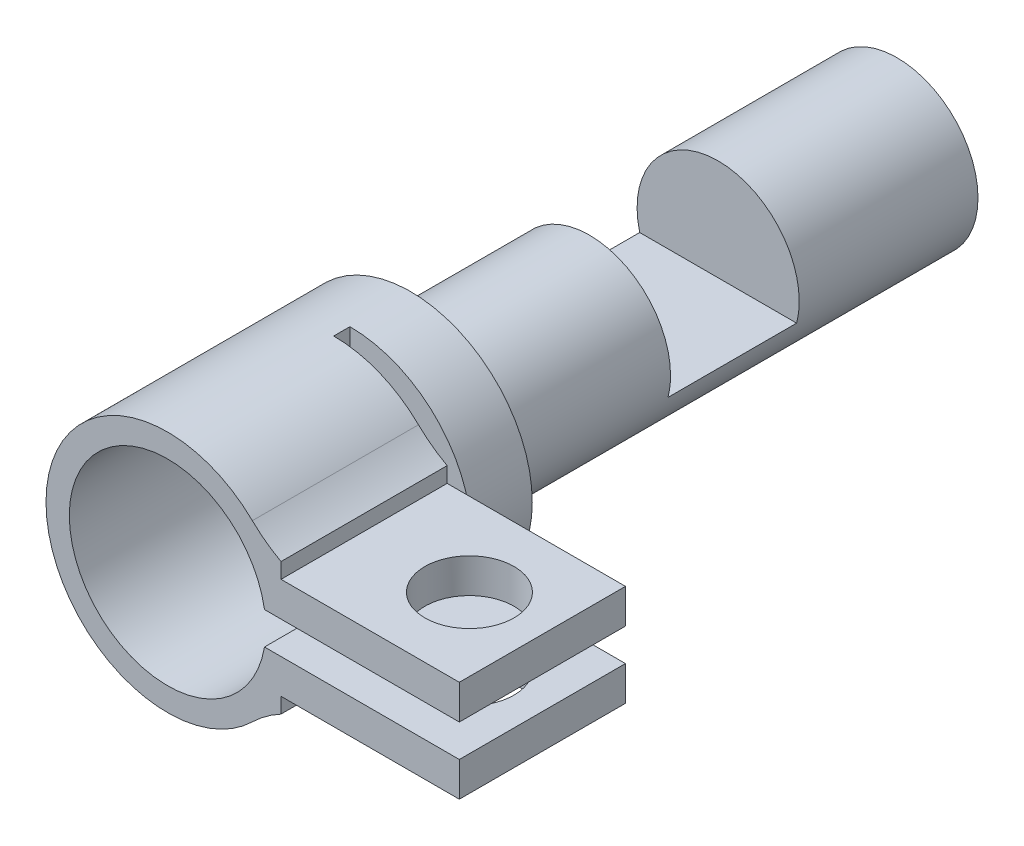
SolidWorks part; units mm, degrees
material "Alloy Steel"
ref_plane "Front" through (0, 0, 0) normal (0, 0, 1) x (1, 0, 0)
ref_plane "Top" through (0, 0, 0) normal (0, 1, 0) x (1, 0, 0)
ref_plane "Right" through (0, 0, 0) normal (1, 0, 0) x (0, 0, -1)
ref_axis "X" through (-80.9, 0, 0) along (1, 0, 0)
ref_axis "Y" through (0, -50, 0) along (0, 1, 0)
ref_axis "Z" through (0, 0, -80.9) along (0, 0, 1)
sketch "Sketch3" plane through (0, 0, 0) normal (1, 0, 0) x (0, 0, -1)
  line L0 (-12.7859, 0) -> (15.8798, 0) construction
  line L1 (18, 0) -> (18, 2)
  line L2 (18, 2) -> (6, 2)
  line L3 (6, 2) -> (6, 3)
  line L4 (6, 3) -> (0, 3)
  line L5 (0, 3) -> (0, 2.425)
  line L6 (0, 2.425) -> (4.5, 2.425)
  line L7 (4.5, 2.425) -> (4.5, 0)
  line L8 (4.5, 0) -> (18, 0)
  dimension "D1" = 12
  dimension "D2" = 4
  dimension "D3" = 4.85
  dimension "D4" = 6
  dimension "D5" = 4.5
  dimension "D6" = 1.5
revolve "Revolve1" add sketch "Sketch3" angle 360 about L0
sketch "Sketch5" plane through (0, 0, 0) normal (0, 1, 0) x (1, 0, 0)
  line L0 (3, 4.5) -> (7.2, 4.5)
  line L1 (7.2, 4.5) -> (7.2, 0)
  line L2 (7.2, 0) -> (3, 0)
  line L3 (3, 0) -> (3, 4.5) construction
  line L4 (2.425, 0) -> (2.425, 4.5)
  line L5 (2.425, 4.5) -> (3, 4.5)
  line L6 (3, 0) -> (2.425, 0)
  line L8 (-2.425, 4.5) -> (2.425, 4.5) construction
  dimension "D1" = 4.2
extrude "Boss-Extrude3" add sketch "Sketch5" along normal mid plane 2.5
sketch "Sketch6" plane through (0, 0, 0) normal (0, 1, 0) x (1, 0, 0)
  line L0 (0, 0) -> (7.2, 0)
  line L1 (7.2, 0) -> (7.2, 4.5)
  line L2 (7.2, 4.5) -> (0, 4.5)
  line L4 (0, 4.5) -> (0, 0)
extrude "Cut-Extrude1" cut sketch "Sketch6" against normal mid plane 0.8
sketch "Sketch7" plane through (0, 0, 0) normal (0, 0, 1) x (1, 0, 0)
  line L0 (0, 5) -> (0, -5)
  line L1 (0, -5) -> (8, -5)
  line L2 (8, -5) -> (8, 5)
  line L3 (8, 5) -> (0, 5)
  dimension "D1" = 10
  dimension "D2" = 8
extrude "Cut-Extrude2" cut sketch "Sketch7" along normal blind 0.4 from surface contours L3 L0 L1 L2 starting at face at (1.485, 0, -4.5)
hole_wizard "M2 Clearance Hole1" positions "Sketch8" profile "Sketch9" hole size "M2" standard "ANSI Metric" end condition through all
sketch "Sketch8" plane through (0, 1.25, 0) normal (0, 1, 0) x (1, 0, 0)
  line L0 (7.2, 2.05) -> (5.4, 2.05) construction
  line L1 (7.2, 0) -> (7.2, 4.1) construction
  point P0 (5.4, 2.05)
  dimension "D1" = 1.8
sketch "Sketch9" plane through (5.4, 1.25, -2.05) normal (1, 0, 0) x (0, 0, 1)
  line L0 (0, 0) -> (0, 4.25)
  line L1 (0, 4.25) -> (1.1, 4.25)
  line L2 (1.1, 4.25) -> (1.1, 0)
  line L5 (1.1, 0) -> (0, 0)
  line L11 (0, -6.35) -> (0, 107.95) construction
  dimension "Thru Hole Dia." = 2.2
  dimension "Thru Hole Depth" = 4.25
sketch "Sketch10" plane through (0, 0, 0) normal (0, 1, 0) x (1, 0, 0)
  line L0 (5, 13.5875) -> (-5, 13.5875)
  line L1 (-5, 13.5875) -> (-5, 10.4125)
  line L2 (-5, 10.4125) -> (5, 10.4125)
  line L3 (5, 10.4125) -> (5, 13.5875)
  line L4 (5, 12) -> (0, 12) construction
  line L6 (0, 12) -> (0, 6) construction
  line L7 (2, 6) -> (-2, 6) construction
  line L8 (0, 12) -> (0, 18) construction
  line L9 (2, 18) -> (-2, 18) construction
  line L10 (0, 12) -> (-5, 12) construction
  dimension "D1" = 3.175
  dimension "D2" = 10
extrude "Cut-Extrude3" cut sketch "Sketch10" along normal through all and the other way blind 0.5
fillet "Fillet1" radius 3.175 2 edges at (2.7272, 1.25, -2.05) (2.7272, -1.25, -2.05)
sketch "Sketch12" plane through (0, 1.25, 0) normal (0, 1, 0) x (1, 0, 0)
  line L0 (7.2, 4.1) -> (2.8, 4.1)
  line L1 (4.307, 4.1) -> (2.0925, 4.1) construction
  line L2 (2.8, 4.1) -> (2.8, 0)
  line L3 (2.0925, 0) -> (4.307, 0) construction
  line L4 (2.8, 0) -> (7.2, 0)
  line L5 (7.2, 0) -> (7.2, 4.1)
  dimension "D1" = 4.4
extrude "Cut-Extrude4" cut sketch "Sketch12" along normal up to next
mirror "Mirror1" about plane through (0, 0, 0) normal (0, 1, 0) of "Cut-Extrude4"
